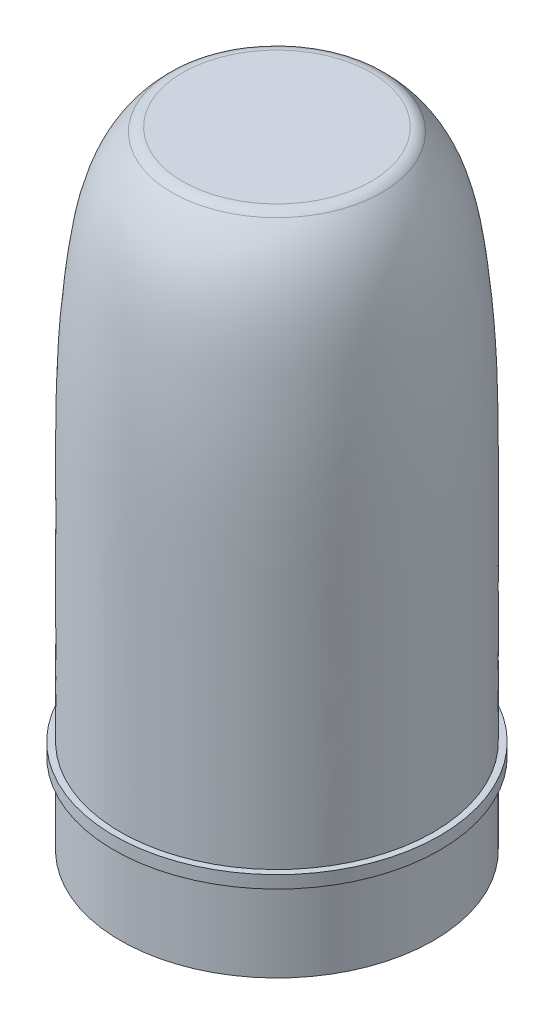
SolidWorks part; units mm, degrees
ref_plane "Front Plane" through (0, 0, 0) normal (0, 0, 1) x (1, 0, 0)
ref_plane "Top Plane" through (0, 0, 0) normal (0, 1, 0) x (1, 0, 0)
ref_plane "Right Plane" through (0, 0, 0) normal (1, 0, 0) x (0, 0, -1)
sketch "Sketch1" plane through (0, 0, 0) normal (0, 0, 1) x (1, 0, 0)
  line L0 (0, 136.0892) -> (0, -80.4462) construction
  line L1 (0, -63.9108) -> (50, -63.9108)
  line L2 (50, -63.9108) -> (50, -37.9108)
  line L3 (50, -37.9108) -> (52, -37.9108)
  line L4 (52, -37.9108) -> (52, -33.9108)
  line L5 (52, -33.9108) -> (50, -33.9108)
  line L6 (0, 136.0892) -> (32, 136.0892)
  line L7 (50, 55.591) -> (50, 22.2332) construction
  line L8 (50, -14.8121) -> (50, -53.2439) construction
  line L9 (0, -63.9108) -> (0, 136.0892)
  spline S0 degree 3 poles (50, -33.9108) (50, -14.8788) (49.977, 15.5938) (50.0284, 66.0335) (49.0348, 90.8657) (43.5244, 126.6155) (32, 136.0892) knots 0 0 0 0 0.316477 0.38837 0.718933 1 1 1 1
  dimension "D1" = 50
  dimension "D2" = 26
  dimension "D3" = 2
  dimension "D4" = 2
  dimension "D5" = 4
  dimension "D6" = 32
  dimension "D7" = 200
  dimension "D8" = 0
  dimension "D9" = 74
  dimension "D10" = 74
revolve "Revolve of Goblet" add sketch "Sketch1" angle 360 about L9
fillet "Top Rounding of Goblet" radius 5 1 edges at (32, 136.0892, 0)
shell "Goblet Hollowing" thickness 2 removed face at (50, -63.9108, 0)
